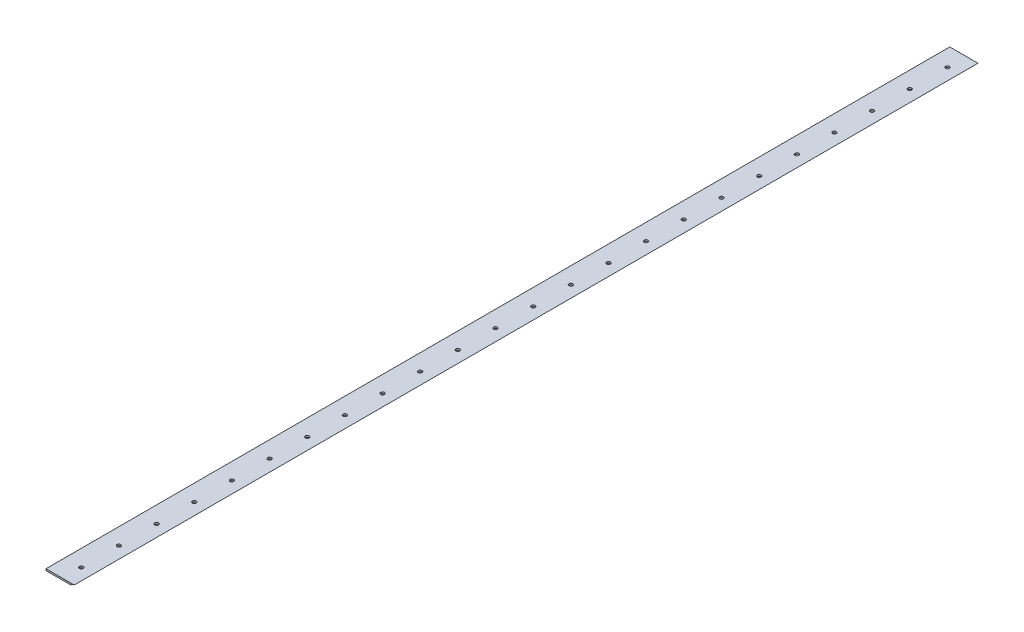
SolidWorks part; units mm, degrees
note: The reader was unsure of these and kept them because the rebuilt part matched: shared geometry of "Sketch1<4>".
material "Plain Carbon Steel"
ref_plane "Front Plane" through (0, 0, 0) normal (0, 0, 1) x (1, 0, 0)
ref_plane "Top Plane" through (0, 0, 0) normal (0, 1, 0) x (1, 0, 0)
ref_plane "Right Plane" through (0, 0, 0) normal (1, 0, 0) x (0, 0, -1)
sketch "Sketch1" plane through (0, 0, 0) normal (0, 0, 1) x (1, 0, 0)
  line L0 (5.461, 5.461) -> (5.461, 43.561)
  line L1 (-38.1, 2.286) -> (0, 2.286)
  line L2 (-38.1, 2.286) -> (-38.1, 0)
  line L3 (-38.1, 0) -> (0, 0)
  line L4 (0, 2.286) -> (0, 0)
  line L5 (5.461, 5.461) -> (3.175, 5.461)
  line L6 (5.461, 43.561) -> (3.175, 43.561)
  line L7 (3.175, 5.461) -> (3.175, 43.561)
  line L9 (0, 10.922) -> (-38.1, 10.922)
  line L10 (0, 10.922) -> (0, 8.636)
  line L11 (0, 8.636) -> (-38.1, 8.636)
  line L12 (-38.1, 10.922) -> (-38.1, 8.636)
  circle A0 centre (0, 5.461) radius 5.461
  dimension "D3" = 10.922
  dimension "D1" = 2.286
  dimension "D2" = 38.1
extrude "Boss-Extrude1" [suppressed] add sketch "Sketch1" along normal mid plane 1219.2 contours A0 L1 L2 L3 | L1 A0 L4 | L7 A0 L10 L11 L1 L4 L5 | L5 A0 L7 | L10 A0 L11
hole_wizard "#10 Clearance Hole2" [suppressed] positions "Sketch8" profile "Sketch7" hole size "#10" standard "ANSI Inch"
sketch "Sketch8" [suppressed] plane through (0, 2.286, 0) normal (0, 1, 0) x (1, 0, 0)
  line L0 (-38.1, -609.6) -> (-38.1, 609.6) construction
  line L1 (-38.1, -609.6) -> (-4.4432, -609.6) construction
  point P0 (-15.875, -584.2)
  dimension "D1" = 22.225
  dimension "D2" = 25.4
sketch "Sketch7" plane through (-15.875, 2.286, 584.2) normal (1, 0, 0) x (0, 0, 1)
  line L0 (0, 0) -> (0, 2.286)
  line L1 (0, 2.286) -> (2.5527, 2.286)
  line L2 (2.5527, 2.286) -> (2.5527, 0)
  line L5 (2.5527, 0) -> (0, 0)
  line L11 (0, -6.35) -> (0, 107.95) construction
  dimension "Thru Hole Dia." = 5.1054
  dimension "Thru Hole Depth" = 2.286
extrude "Boss-Extrude3" add sketch "Sketch1<4>" along normal mid plane 1219.2 contours A0 L9 L12 L11
sketch "Sketch1<4>" plane through (0, 0, 0) normal (0, 0, 1) x (1, 0, 0) same geometry as "Sketch1"
hole_wizard "#10 Clearance Hole3" positions "Sketch10" profile "Sketch9" hole size "#10" standard "ANSI Inch" end condition through all
sketch "Sketch10" plane through (0, 10.922, 0) normal (0, 1, 0) x (1, 0, 0)
  line L0 (0, -609.6) -> (-38.1, -609.6) construction
  line L1 (-38.1, -609.6) -> (-38.1, 609.6) construction
  point P0 (-15.875, -584.2)
  dimension "D1" = 25.4
  dimension "D2" = 22.225
sketch "Sketch9" plane through (-15.875, 10.922, 584.2) normal (1, 0, 0) x (0, 0, 1)
  line L0 (0, 0) -> (0, 2.286)
  line L1 (0, 2.286) -> (2.5527, 2.286)
  line L2 (2.5527, 2.286) -> (2.5527, 0)
  line L5 (2.5527, 0) -> (0, 0)
  line L11 (0, -6.35) -> (0, 107.95) construction
  dimension "Thru Hole Dia." = 5.1054
  dimension "Thru Hole Depth" = 2.286
pattern_linear "LPattern1" count 24 spacing 50.8 along (0, 0, -1) of "#10 Clearance Hole3"
pattern_linear "LPattern2" [suppressed] count 24 spacing 50.8
equation "\"4f\"=0.1"
